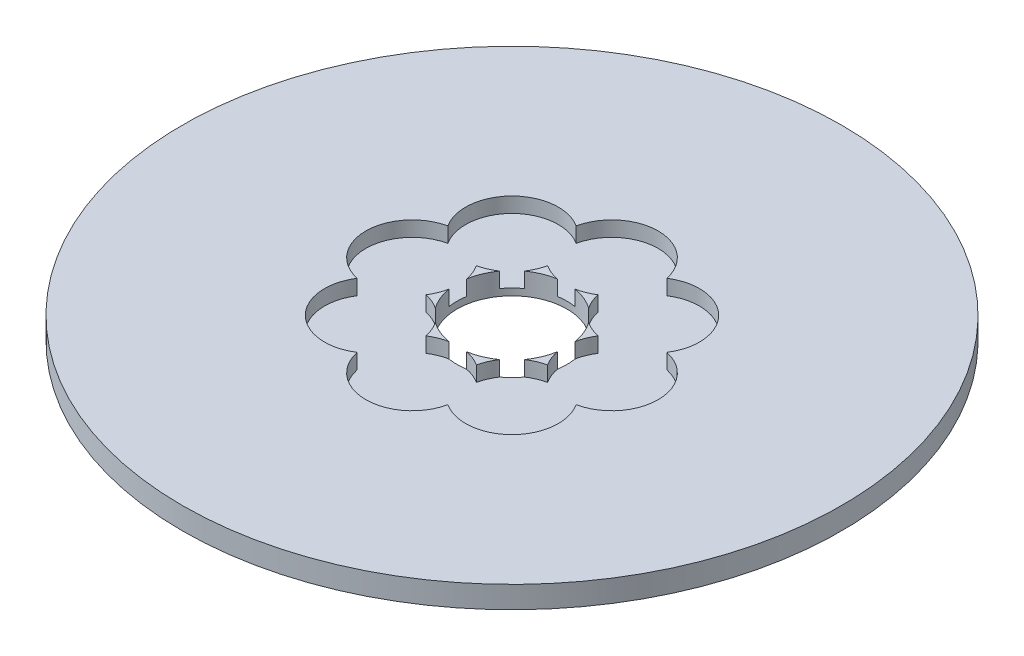
SolidWorks part; units mm, degrees
ref_plane "Front Plane" through (0, 0, 0) normal (0, 0, 1) x (1, 0, 0)
ref_plane "Top Plane" through (0, 0, 0) normal (0, 1, 0) x (1, 0, 0)
ref_plane "Right Plane" through (0, 0, 0) normal (1, 0, 0) x (0, 0, -1)
sketch "Sketch1" plane through (0, 0, 0) normal (0, 1, 0) x (1, 0, 0)
  circle A0 centre (0, 0) radius 60
  dimension "FLANGE_OD" = 120
extrude "Boss-Extrude1" add sketch "Sketch1" along normal blind 4
sketch "Sketch2" plane through (0, 0, 0) normal (0, 1, 0) x (1, 0, 0)
  circle A0 centre (0, 0) radius 10
  dimension "BORE_D" = 20
extrude "Cut-Extrude1" cut sketch "Sketch2" along normal through all
sketch "Sketch3" plane through (0, 4, 0) normal (0, 1, 0) x (1, 0, 0)
  circle A0 centre (0, 0) radius 18.1644 construction
  circle A1 centre (-18.1644, 0) radius 8.4468
  dimension "BOLT_D" = 16.8936
  dimension "BOLT_PCD" = 36.3288
extrude "Cut-Extrude2" cut sketch "Sketch3" against normal blind 2.7559
pattern_circular "CirPattern1" count 8 over 360 about axis through (0, 0, 0) along (0, 1, 0) of "Cut-Extrude2"
